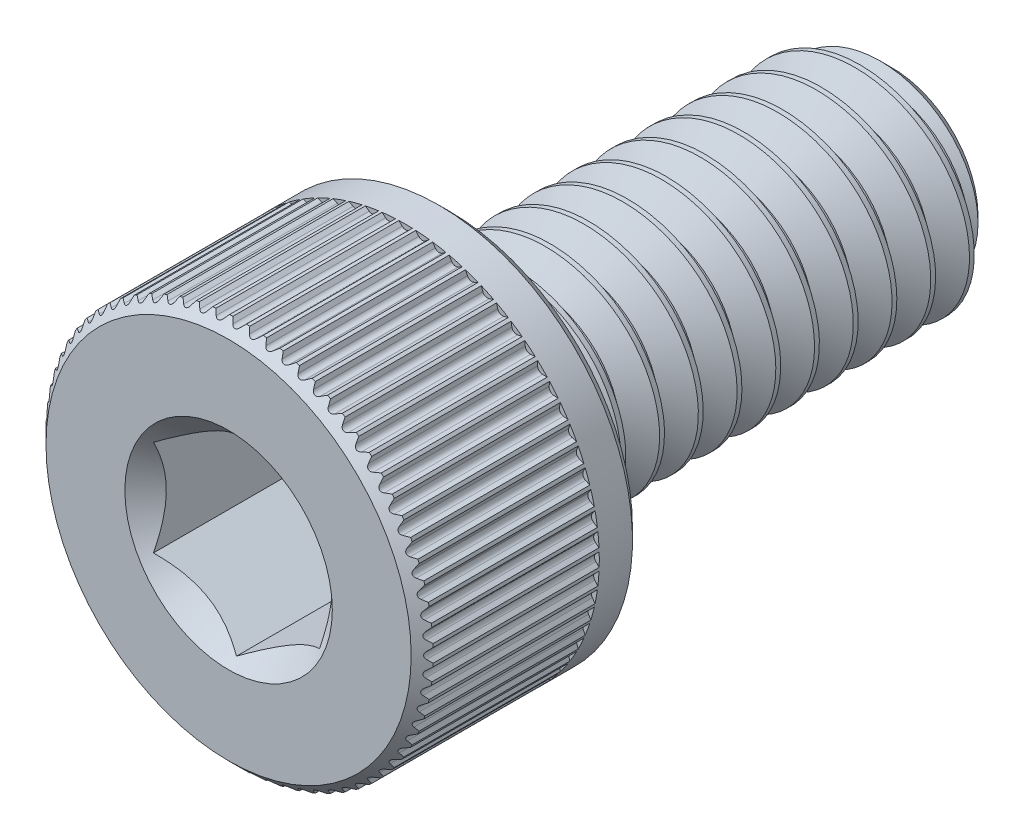
SolidWorks part; units mm, degrees
ref_plane "Front Plane" through (0, 0, 0) normal (0, 0, 1) x (1, 0, 0)
ref_plane "Top Plane" through (0, 0, 0) normal (0, 1, 0) x (1, 0, 0)
ref_plane "Right Plane" through (0, 0, 0) normal (1, 0, 0) x (0, 0, -1)
sketch "Sketch1" plane through (0, 0, 0) normal (1, 0, 0) x (0, 0, -1)
  line L0 (-6, 0) -> (6, 0) construction
  line L1 (6, 0) -> (6, 1.5453) construction
  line L2 (6, 1.5453) -> (5.5453, 2) construction
  line L3 (5.5453, 2) -> (5.475, 2) construction
  line L4 (5.475, 2) -> (-2, 2) construction
  line L5 (-2, 2) -> (-2, 3.5) construction
  line L6 (-2, 3.5) -> (-6, 3.5) construction
  line L7 (-6, 3.5) -> (-6, 0) construction
  line L8 (6, 1.5453) -> (6, 2) construction
  line L9 (5.9562, 2.0758) -> (6.3062, 1.4696) construction
  line L10 (6.3062, 1.4696) -> (6.6562, 2.0758) construction
  line L11 (6.6562, 2.0758) -> (5.9562, 2.0758) construction
  line L12 (6.3062, 2.0758) -> (6.3062, 2) construction
  line L13 (6.3062, 1.4696) -> (6.3062, 1.5453) construction
  line L14 (6.2625, 1.5453) -> (6.35, 1.5453) construction
  line L15 (6, 2) -> (6.6125, 2) construction
  line L16 (5.9781, 2.0379) -> (6.6344, 2.0379) construction
  line L17 (6, 0) -> (6, -2) construction
  line L18 (-2.2, 3.5) -> (-2, 3.3) construction
  line L19 (-5.8, 3.5) -> (-6, 3.3) construction
  line L20 (-2, 2) -> (-2, 0) construction
  line L21 (-2, 1) -> (0.6667, 1) construction
  line L22 (0.6667, 1) -> (3.3333, 1) construction
  line L23 (3.3333, 1) -> (6, 1) construction
  line L24 (0.6667, 1) -> (0.6667, 2) construction
  line L25 (0.6667, 2) -> (0.6667, 3.5) construction
  line L26 (3.3333, 1) -> (3.3333, 3.5) construction
  point P0 (-6, 1.5)
  point P3 (4.25, 2)
  point P4 (0, 0)
  point P18 (3.3333, 2)
  point P22 (6.3062, 1.5453)
  point P24 (5.475, 2)
  point P25 (6.3062, 2)
  point P28 (6.3062, 2.0379)
  point P29 (4.25, -2)
  point P30 (0.6667, 2)
  point P31 (-4, 3.5)
  point P37 (-2.7, 3.5)
  point P38 (-5.7, 3.5)
  point P45 (0.6667, 1)
  point P46 (3.3333, 1)
  dimension "D2" = 0.0875
  dimension "D7" = 0.2
  dimension "D8" = 0.2
  dimension "D9" = 0.2
  dimension "D10" = 0.1
  dimension "D11" = 0.5
  dimension "Drive Size" = 3
  dimension "Head Diameter" = 7
  dimension "Head Height" = 4
  dimension "Thread Pitch" = 0.7
  dimension "Thread Size" = 4
  dimension "Length" = 8
  dimension "D12" = 0.525
  dimension "D4" = 1.75
  dimension "D3" = 45
sketch "Sketch2" plane through (0, 0, 0) normal (1, 0, 0) x (0, 0, -1)
  line L0 (-6, 0) -> (-6, 3.3)
  line L1 (-5.8, 3.5) -> (-2.2, 3.5)
  line L2 (-2, 3.3) -> (-2, 2.2)
  line L4 (5.5453, 2) -> (6, 1.5453)
  line L5 (6, 1.5453) -> (6, 0)
  line L6 (-2, 3.5) -> (-6, 3.5) construction
  line L7 (6, 0) -> (-6, 0)
  line L8 (-5.8, 3.5) -> (-6, 3.3) construction
  line L10 (-5.8, 3.5) -> (-6, 3.3)
  line L14 (-2.2, 3.5) -> (-2, 3.3) construction
  line L16 (-2.2, 3.5) -> (-2, 3.3)
  line L17 (-2, 2) -> (-2, 3.5) construction
  line L19 (-1.8, 2) -> (5.5453, 2)
  line L20 (5.475, 2) -> (-2, 2) construction
  arc A1 (-2, 2.2) -> (-1.8, 2) centre (-1.8, 2.2) ccw
  dimension "D3" = 0.2
revolve "Revolve1" add sketch "Sketch2" angle 360 about L7
sketch "Sketch3" plane through (0, 0, 6) normal (0, 0, 1) x (1, 0, 0)
  line L1 (1.5, -0.866) -> (1.5, 0.866)
  line L2 (1.5, 0.866) -> (0, 1.7321)
  line L3 (0, 1.7321) -> (-1.5, 0.866)
  line L4 (-1.5, 0.866) -> (-1.5, -0.866)
  line L5 (-1.5, -0.866) -> (0, -1.7321)
  line L6 (0, -1.7321) -> (1.5, -0.866)
  circle A0 centre (0, 0) radius 1.5 construction
  circle A1 centre (0, 0) radius 3.5 construction
  circle A2 centre (0, 0) radius 3.5 construction
  circle A3 centre (0, 0) radius 1.7321 construction
  point P13 (0, 0)
extrude "Cut-Extrude1" cut sketch "Sketch3" against normal offset from surface (3 mm away) 1 up to face at (0, 3.3, 2)
sketch "Sketch4" plane through (0, 0, 6) normal (0, 0, 1) x (1, 0, 0)
  circle A0 centre (0, 0) radius 1.875
  dimension "D1" = 3.75
extrude "Cut-Extrude2" cut sketch "Sketch4" against normal up to vertex (2 mm away) draft 45 up to point (0, 3.5, 4)
sketch "Sketch11" plane through (0, 0, 0) normal (1, 0, 0) x (0, 0, -1)
  line L0 (-6, 0) -> (6, 0) construction
  line L1 (-6, 0) -> (6, 0) construction
  line L2 (-0.5, 0) -> (-0.5, 2) construction
  line L3 (5.475, 2) -> (-2, 2) construction
  line L4 (4.5, 0) -> (4.5, 2) construction
  line L6 (6, 1.5453) -> (6, 2) construction
  point P2 (-0.5, 0)
  point P3 (4.5, 0)
  dimension "D1" = 1.5
  dimension "D2" = 1.5
sketch "Sketch6" plane through (0, 0, -6) normal (0, 0, -1) x (-1, 0, 0)
  circle A0 centre (0, 0) radius 2
curve "Helix/Spiral1" pitch 0.7 height 8.7 radius 2 centre (0, 0, -6) axis (0, 0, 1) start towards (0, 1, 0)
sketch "Sketch10" plane through (0, 0, 0) normal (1, 0, 0) x (0, 0, -1)
  line L0 (-1.8, -3.5) -> (-1.8, 3.5)
  line L5 (-6, 0) -> (6, 0) construction
  line L6 (-1.8, 2) -> (-1.8, -2) construction
  point P3 (-1.8, 0)
split "Split1" trim tools "Sketch10" bodies to split 106 resulting bodies 114 115
sketch "Sketch7" plane through (0, 0, 0) normal (1, 0, 0) x (0, 0, -1)
  line L0 (5.9781, 2.0379) -> (6.6344, 2.0379)
  line L1 (6.6344, 2.0379) -> (6.35, 1.5453)
  line L2 (6.35, 1.5453) -> (6.2625, 1.5453)
  line L3 (6.2625, 1.5453) -> (5.9781, 2.0379)
sweep "Cut-Sweep1" cut profiles "Sketch7" path "Helix/Spiral1" align with end faces yes
sketch "Sketch8" plane through (0, 0, 0) normal (1, 0, 0) x (0, 0, -1)
  line L0 (-2, 0) -> (-2, 2)
  line L1 (-1.8, -2) -> (-1.8, 2) construction
  line L2 (-2, 2) -> (-1.8, 2)
  line L4 (-1.8, 2) -> (-0.6453, 0)
  line L5 (-0.6453, 0) -> (-2, 0)
  line L6 (5.475, 2) -> (-2, 2) construction
  line L7 (-6, 0) -> (6, 0) construction
  dimension "D1" = 60
revolve "Revolve2" add sketch "Sketch8" angle 360 about L5
ref_plane "Plane1" through (0, 0, 6) normal (0, 0, 1) x (1, 0, 0)
sketch "Sketch12" plane through (0, 0, 6) normal (0, 0, 1) x (1, 0, 0)
  line L0 (0, 0) -> (0.1221, 3.4979) construction
  line L1 (0, 0) -> (-0.1221, 3.4979) construction
  line L2 (0, 3.4125) -> (0, 3.5875) construction
  line L3 (-0.2118, 3.5875) -> (0.2118, 3.5875)
  line L4 (-0.2118, 3.5875) -> (-0.0628, 3.4385)
  line L5 (0.0628, 3.4385) -> (0.2118, 3.5875)
  circle A0 centre (0, 0) radius 3.5 construction
  arc A1 (-0.0628, 3.4385) -> (0.0628, 3.4385) centre (0, 3.5013) ccw
  point P9 (0, 3.5875)
  point P13 (0, 3.5)
  dimension "D2" = 0.0875
extrude "Cut-Extrude3" cut sketch "Sketch12" against normal blind 3.2
pattern_circular "CirPattern1" count 72 over 360 about axis through (0, 0, 6) along (0, 0, -1) of "Cut-Extrude3"
equation "\"D2@Sketch1\" = \"Thread Pitch@Sketch1\" / 8"
equation "\"D4@Helix/Spiral1\" = \"Thread Pitch@Sketch1\""
equation "\"D7@Sketch1\" = \"Head Height@Sketch1\" * .05"
equation "\"D8@Sketch1\"=\"D7@Sketch1\""
equation "\"D9@Sketch1\"=\"D7@Sketch1\""
equation "\"D10@Sketch1\"=\"D7@Sketch1\"/2"
equation "\"D11@Sketch1\"=\"D10@Sketch1\"*5"
equation "\"D4@Sketch1\"=\"Thread Pitch@Sketch1\"*2.5"
equation "\"D12@Sketch1\"=\"Thread Pitch@Sketch1\"*.75"
equation "\"D3@Helix/Spiral1\"=\"Length@Sketch1\"+\"Thread Pitch@Sketch1\""
equation "\"D3@Sketch2\" = \"Thread Size@Sketch1\" * 0.05"
equation "\"D1@Sketch11\"=\"Length@Sketch1\"*0.1875"
equation "\"D2@Sketch11\"=\"D1@Sketch11\""
equation "\"D2@Sketch12\"=\"Head Diameter@Sketch1\"*.0125"
equation "\"D1@Cut-Extrude3\"=\"Head Height@Sketch1\"*.8"
equation "\"D1@CirPattern1\"=\"D3@CirPattern1\"/(1.25*\"D1@Sketch12\")"
equation "\"D1@Sketch4\"=\"Drive Size@Sketch1\"*1.25"
